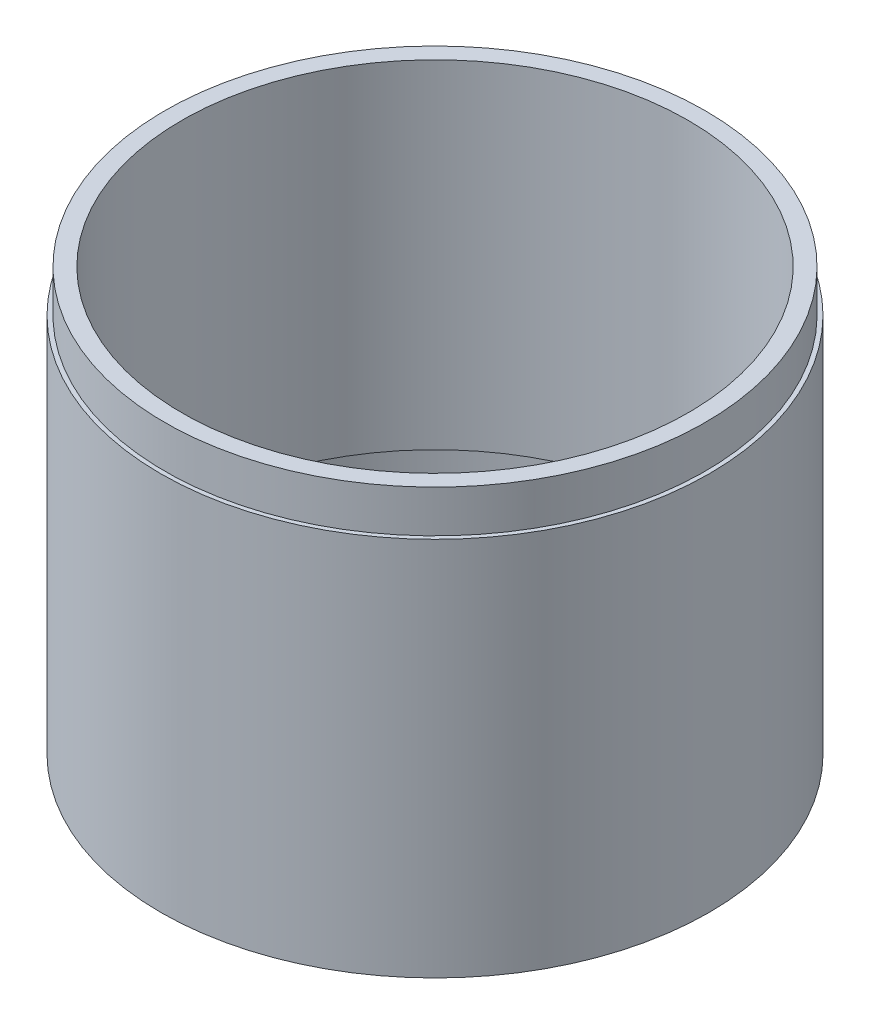
SolidWorks part; units mm, degrees
material "HYPALON"
ref_plane "Front Plane" through (0, 0, 0) normal (0, 0, 1) x (1, 0, 0)
ref_plane "Top Plane" through (0, 0, 0) normal (0, 1, 0) x (1, 0, 0)
ref_plane "Right Plane" through (0, 0, 0) normal (1, 0, 0) x (0, 0, -1)
sketch "Szkic1" plane through (0, 0, 0) normal (0, 0, 1) x (1, 0, 0)
  line L0 (0, 0) -> (-65, 0)
  line L1 (-65, 0) -> (-65, 20)
  line L2 (-62, 20) -> (-60, 20)
  line L3 (-60, 20) -> (-60, 100)
  line L4 (-62, 20) -> (-62, 0)
  line L5 (-60, 100) -> (-64, 100)
  line L7 (-65, 20) -> (-65, 90)
  line L8 (-65, 90) -> (-64, 90)
  line L9 (-64, 90) -> (-64, 100)
  line L13 (0, 0) -> (0, 22.4148)
  dimension "D1" = 65
  dimension "D2" = 20
  dimension "D3" = 62
  dimension "D4" = 100
  dimension "D7" = 1
  dimension "D8" = 10
  dimension "D13" = 2
revolve "Obrót1" add sketch "Szkic1" angle 360 about L13 region at (-62.5889, 52.5556, 0)
